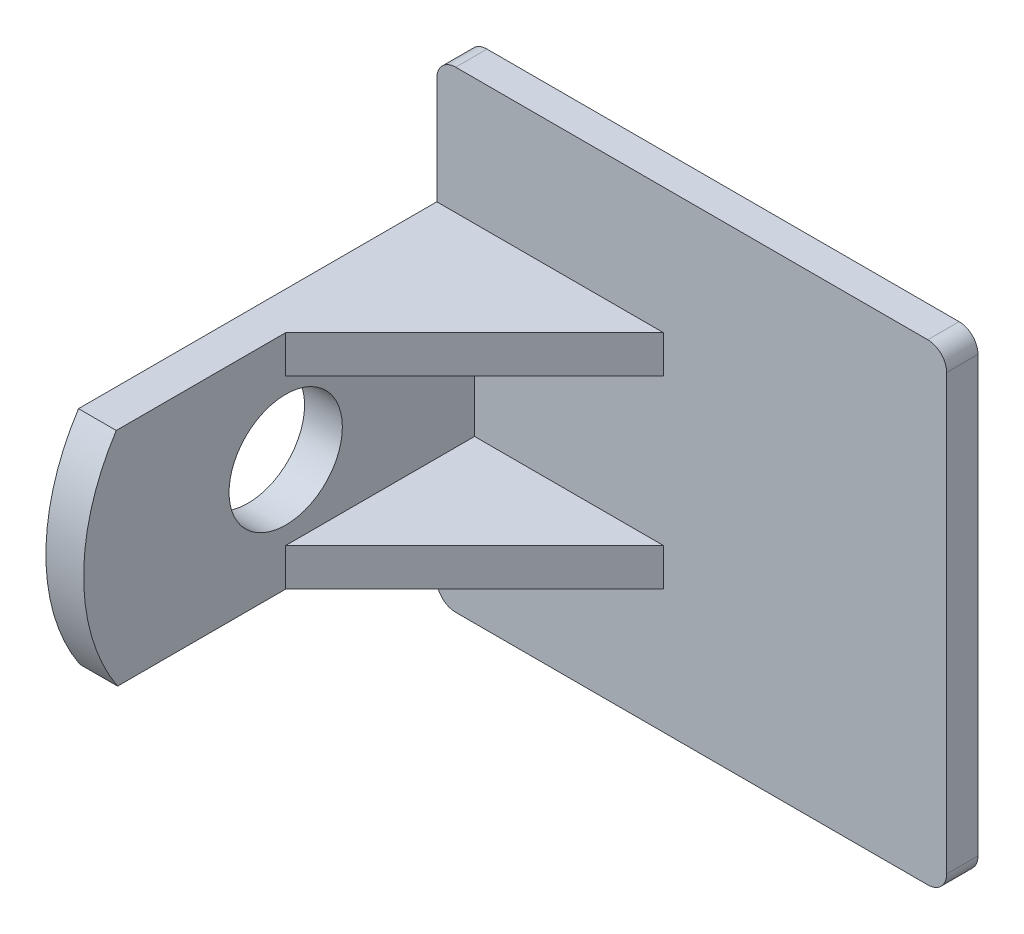
SolidWorks part; units mm, degrees
ref_plane "前视基准面" through (0, 0, 0) normal (0, 0, 1) x (1, 0, 0)
ref_plane "上视基准面" through (0, 0, 0) normal (0, 1, 0) x (1, 0, 0)
ref_plane "右视基准面" through (0, 0, 0) normal (1, 0, 0) x (0, 0, -1)
sketch "草图1" plane through (0, 0, 0) normal (1, 0, 0) x (0, 0, -1)
  line L0 (11.6587, 5.8267) -> (11.6587, -5.9348)
  line L1 (-8.3413, 5.8267) -> (11.6587, 5.8267)
  line L2 (0, -5.9348) -> (11.6587, -5.9348)
  line L3 (-8.3413, 5.8267) -> (-8.9725, 5.8267)
  line L4 (0, -5.9348) -> (-8.9885, -5.9348)
  circle A0 centre (0, 0) radius 3
  arc A3 (-8.9725, 5.8267) -> (-8.9014, -5.9348) centre (0, 0) ccw
  dimension "D1" = 6
  dimension "D2" = 20
extrude "凸台-拉伸1" add sketch "草图1" along normal blind 2 contours L1 L2 L0 A0 region at (0, -0.054, -11.4061)
sketch "草图2" plane through (2, 0, 0) normal (1, 0, 0) x (0, 0, -1)
  line L0 (10, 12.5) -> (10, -12.5)
  line L1 (10, -12.5) -> (11.6587, -12.5)
  line L2 (11.6587, -12.5) -> (11.6587, 12.5)
  line L3 (11.6587, 12.5) -> (10, 12.5)
  line L4 (0, 0) -> (3, 0) construction
  line L5 (11.6587, 5.8267) -> (11.6587, -5.9348) construction
  circle A0 centre (0, 0) radius 3 construction
  point P4 (10, 0)
  dimension "D1" = 25
  dimension "D2" = 10
  dimension "D3" = 0
extrude "凸台-拉伸2" add sketch "草图2" along normal blind 25
sketch "草图3" plane through (0, 5.8267, 0) normal (0, 1, 0) x (1, 0, 0)
  line L0 (2, 0) -> (12, 10)
  line L1 (2, 10) -> (2, -8.9725) construction
  line L2 (12, 10) -> (2, 10)
  line L3 (2, 10) -> (2, 0)
  dimension "D1" = 10
  dimension "D2" = 10
extrude "凸台-拉伸3" add sketch "草图3" against normal blind 2
sketch "草图4" plane through (0, -5.9348, -5.9348) normal (0, 1, 0) x (1, 0, 0)
  line L0 (2, -5.9348) -> (12, 4.0652)
  line L2 (12, 4.0652) -> (2, 4.0652)
  line L3 (2, 4.0652) -> (2, -5.9348)
  line L4 (2, 4.0652) -> (2, -14.8362) construction
  point P2 (2, 4.0652)
  dimension "D1" = 10
  dimension "D2" = 10
extrude "凸台-拉伸4" add sketch "草图4" along normal blind 2
sketch "草图5" plane through (2, 0, 0) normal (-1, 0, 0) x (0, 0, 1)
  line L1 (-11.6587, 12.5) -> (-10, 12.5)
  line L2 (-11.6587, 12.5) -> (-11.6587, -12.5)
  line L3 (-11.6587, -12.5) -> (-10, -12.5)
  line L4 (-10, 12.5) -> (-10, -12.5)
extrude "凸台-拉伸5" add sketch "草图5" along normal blind 2
fillet "圆角1" radius 1 4 edges at (0, 12.5, -10.8293) (27, 12.5, -10.8293) (27, -12.5, -10.8293) (0, -12.5, -10.8293)
